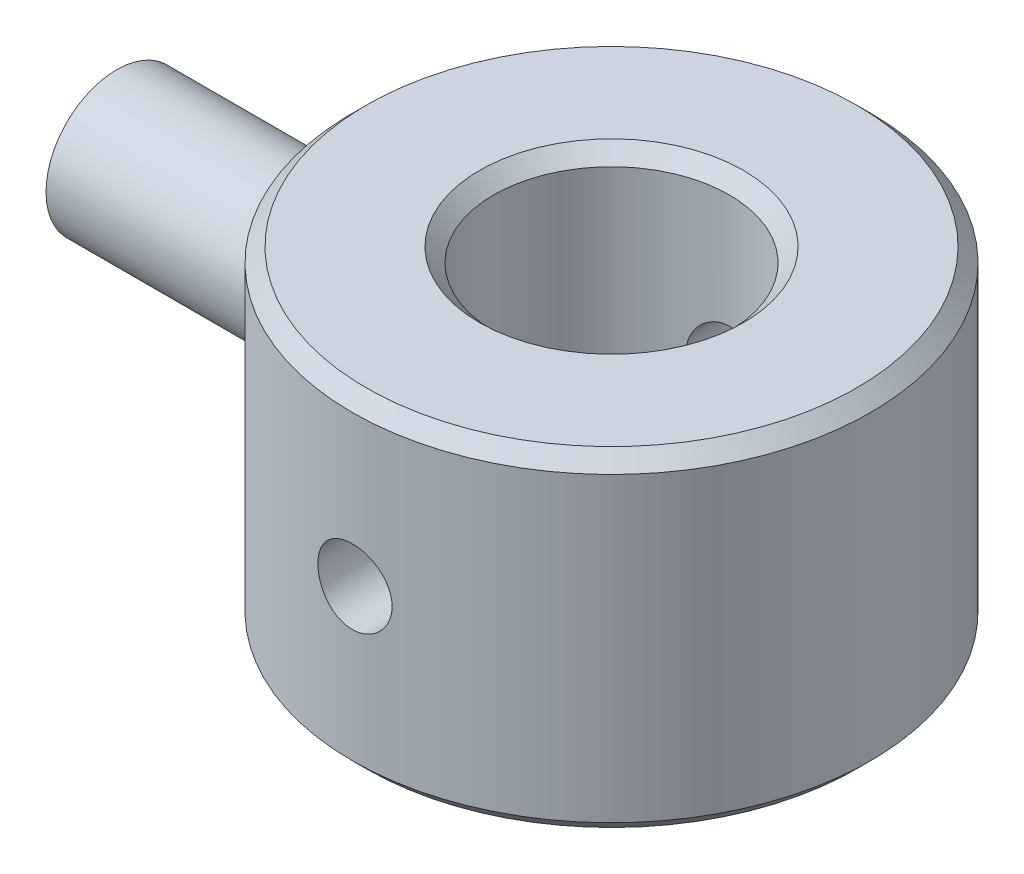
SolidWorks part; units mm, degrees
ref_plane "Front Plane" through (0, 0, 0) normal (0, 0, 1) x (1, 0, 0)
ref_plane "Top Plane" through (0, 0, 0) normal (0, 1, 0) x (1, 0, 0)
ref_plane "Right Plane" through (0, 0, 0) normal (1, 0, 0) x (0, 0, -1)
sketch "Sketch1" plane through (0, 0, 0) normal (0, 1, 0) x (1, 0, 0)
  circle A0 centre (0, 0) radius 3.175
  circle A1 centre (0, 0) radius 6.985
  dimension "D1" = 6.35
  dimension "D2" = 13.97
extrude "Boss-Extrude1" add sketch "Sketch1" along normal blind 8.89
sketch "Sketch2" plane through (0, 0, 0) normal (0, 0, 1) x (1, 0, 0)
  line L0 (0, 8.89) -> (0, 0) construction
  line L1 (6.985, 8.89) -> (-6.985, 8.89) construction
  line L2 (-6.985, 4.445) -> (6.985, 4.445) construction
  line L3 (-6.985, 8.89) -> (-6.985, 0) construction
  line L4 (6.985, 0) -> (6.985, 8.89) construction
  circle A0 centre (0, 4.445) radius 1
  dimension "D1" = 2
extrude "Cut-Extrude1" cut sketch "Sketch2" against normal mid plane 25.4
ref_plane "Plane1" through (-6.985, 0, 0) normal (-1, 0, 0) x (0, 0, 1)
ref_plane "Plane2" through (-4.445, 0, 0) normal (-1, 0, 0) x (0, 0, 1)
sketch "Sketch3" plane through (-4.445, 0, 0) normal (-1, 0, 0) x (0, 0, 1)
  line L0 (0, 8.89) -> (0, -49991.11) construction
  line L1 (6.985, 8.89) -> (-6.985, 8.89) construction
  line L2 (6.985, 4.445) -> (-49993.015, 4.445) construction
  line L4 (-6.985, 8.89) -> (-6.985, 0) construction
  line L5 (-6.985, 4.445) -> (6.985, 4.445) construction
  line L6 (6.985, 8.89) -> (6.985, 0) construction
  circle A0 centre (0, 4.445) radius 1.905
  point P4 (0, 8.89)
  point P18 (0, 0)
  point P19 (0, 0)
  point P20 (0, 0)
  dimension "D1" = 3.81
extrude "Boss-Extrude2" add sketch "Sketch3" along normal blind 8.89
fillet "Fillet1" radius 1.27 1 edges at (-6.7299, 4.8062, 1.8704)
chamfer "Chamfer1" distance 0.381 angle 45 4 edges at (0, 0, 3.175) (0, 0, 6.985) (0, 8.89, 6.985) (0, 8.89, 3.175)
